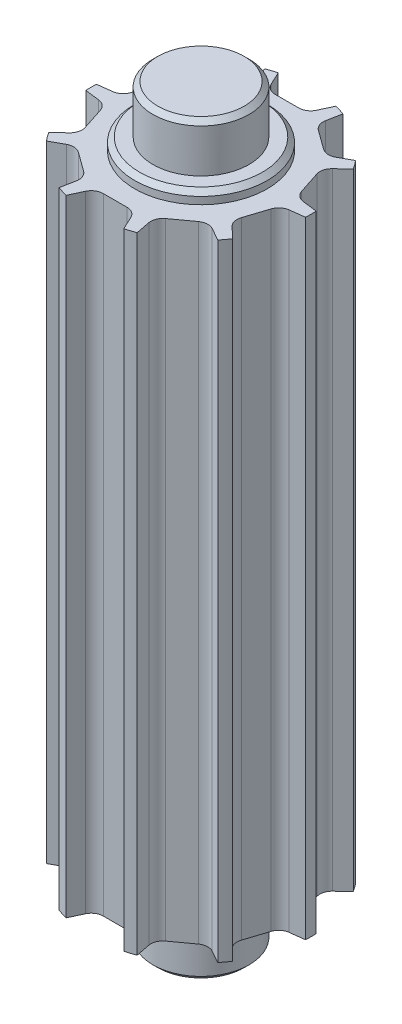
SolidWorks part; units mm, degrees
material "6061-T6 (SS)"
ref_plane "Ebene vorne" through (0, 0, 0) normal (0, 0, 1) x (1, 0, 0)
ref_plane "Ebene oben" through (0, 0, 0) normal (0, 1, 0) x (1, 0, 0)
ref_plane "Ebene rechts" through (0, 0, 0) normal (1, 0, 0) x (0, 0, -1)
ref_axis "Achse1" through (0, -1.8269, 0) along (0, 1, 0)
sketch "Skizze1" plane through (0, 0, 0) normal (0, 1, 0) x (1, 0, 0)
  circle A0 centre (0, 0) radius 4.57
  dimension "D1" = 9.14
extrude "Aufsatz-Linear austragen1" add sketch "Skizze1" along normal blind 31
sketch "Skizze12" plane through (0, 31, 0) normal (0, 1, 0) x (1, 0, 0)
  line L0 (0, 9.2022) -> (0, -8.7185) construction
  line L1 (-8.4713, 0) -> (7.9602, 0) construction
  line L2 (-1.2, 4.4096) -> (-0.8085, 3.57)
  line L3 (1.2, 4.4096) -> (0.8085, 3.57)
  line L4 (-2.6848, 4.57) -> (2.3241, 4.57) construction
  line L5 (-0.8085, 3.57) -> (0.8085, 3.57)
  circle A0 centre (0, 0) radius 3.57 construction
  circle A1 centre (0, 0) radius 4.57 construction
  circle A2 centre (0, 0) radius 4.57 construction
  arc A4 (-1.2, 4.4096) -> (1.2, 4.4096) centre (0, 0) cw
  dimension "D1" = 7.14
  dimension "D6" = 9.14
  dimension "D2" = 2.4
  dimension "D3" = 50
  dimension "D4" = 1.6169
  dimension "D7" = 1
extrude "Schnitt-Linear austragen1" cut sketch "Skizze12" against normal through all
fillet "Verrundung1" radius 0.5 2 edges at (-0.8085, 15.5, -3.57) (0.8085, 15.5, -3.57)
pattern_circular "Kreismuster1" count 10 over 360 about axis through (0, -1.8269, 0) along (0, 1, 0) of "Schnitt-Linear austragen1", "Verrundung1"
sketch "Skizze13" plane through (0, 0, 0) normal (1, 0, 0) x (0, 0, -1)
  line L0 (0, -5.6077) -> (0, 23.9636) construction
  line L1 (-1.995, 0) -> (-10.0768, 0)
  line L2 (-1.995, 0) -> (-1.995, 2)
  line L3 (-1.995, 2) -> (-2.75, 2)
  line L4 (-2.75, 2) -> (-2.75, 2.5)
  line L5 (-2.75, 2.5) -> (-6.4509, 2.5)
  line L6 (-6.4509, 2.5) -> (-6.4509, 28.5)
  line L7 (-6.4509, 28.5) -> (-2.75, 28.5)
  line L8 (-2.75, 28.5) -> (-2.75, 29)
  line L9 (-2.75, 29) -> (-1.995, 29)
  line L10 (-1.995, 29) -> (-1.995, 31)
  line L11 (-10.0768, 0) -> (-10.0768, 31)
  line L12 (-10.0768, 31) -> (-1.995, 31)
  line L14 (0.6372, 31) -> (1.5691, 31) construction
  point P17 (-6.0359, 31)
  dimension "D1" = 3.99
  dimension "D2" = 2
  dimension "D3" = 2
  dimension "D4" = 2.5
  dimension "D5" = 2.5
  dimension "D6" = 5.5
revolve "Schnitt-Rotation1" cut sketch "Skizze13" angle 360 about L0
chamfer "Fase1" distance 0.2 angle 45 4 edges at (0, 0, -1.995) (0, 2, -2.75) (0, 29, -2.75) (0, 31, -1.995)
sketch "Skizze14" plane through (0, 0, 0) normal (1, 0, 0) x (0, 0, -1)
  line L0 (0, -2.8162) -> (0, 4.9138) construction
  line L1 (-4.1884, 0) -> (4.9626, 0) construction
  line L2 (0, 0) -> (-0.6, 0)
  line L3 (-0.6, 0) -> (-0.6, 1.5)
  line L4 (-0.6, 1.5) -> (0, 1.7485)
  line L5 (0, 1.7485) -> (0, 0)
  dimension "D1" = 1.2
  dimension "D2" = 1.5
  dimension "D3" = 67.5
revolve "Schnitt-Rotation2" cut sketch "Skizze14" angle 360 about L0
